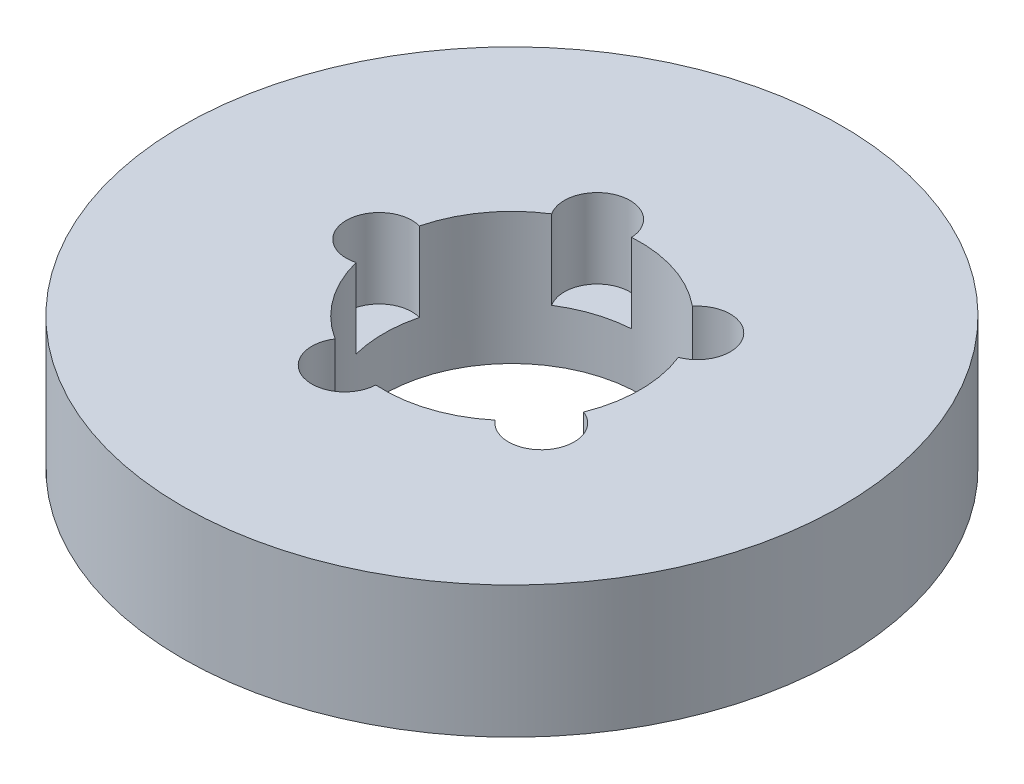
SolidWorks part; units mm, degrees
ref_plane "Front Plane" through (0, 0, 0) normal (0, 0, 1) x (1, 0, 0)
ref_plane "Top Plane" through (0, 0, 0) normal (0, 1, 0) x (1, 0, 0)
ref_plane "Right Plane" through (0, 0, 0) normal (1, 0, 0) x (0, 0, -1)
sketch "Sketch1" plane through (0, 0, 0) normal (0, 1, 0) x (1, 0, 0)
  circle A0 centre (0, 0) radius 45
  dimension "FLANGE_OD" = 90
extrude "Boss-Extrude1" add sketch "Sketch1" along normal blind 18
sketch "Sketch2" plane through (0, 0, 0) normal (0, 1, 0) x (1, 0, 0)
  circle A0 centre (0, 0) radius 17.5
  dimension "BORE_D" = 35
extrude "Cut-Extrude1" cut sketch "Sketch2" along normal through all
sketch "Sketch3" plane through (0, 18, 0) normal (0, 1, 0) x (1, 0, 0)
  circle A0 centre (0, 0) radius 18.1264 construction
  circle A1 centre (-18.1264, 0) radius 4.4834
  dimension "BOLT_D" = 8.9667
  dimension "BOLT_PCD" = 36.2527
extrude "Cut-Extrude2" cut sketch "Sketch3" against normal blind 10.8192
pattern_circular "CirPattern1" count 5 over 360 about axis through (0, 0, 0) along (0, 1, 0) of "Cut-Extrude2"
